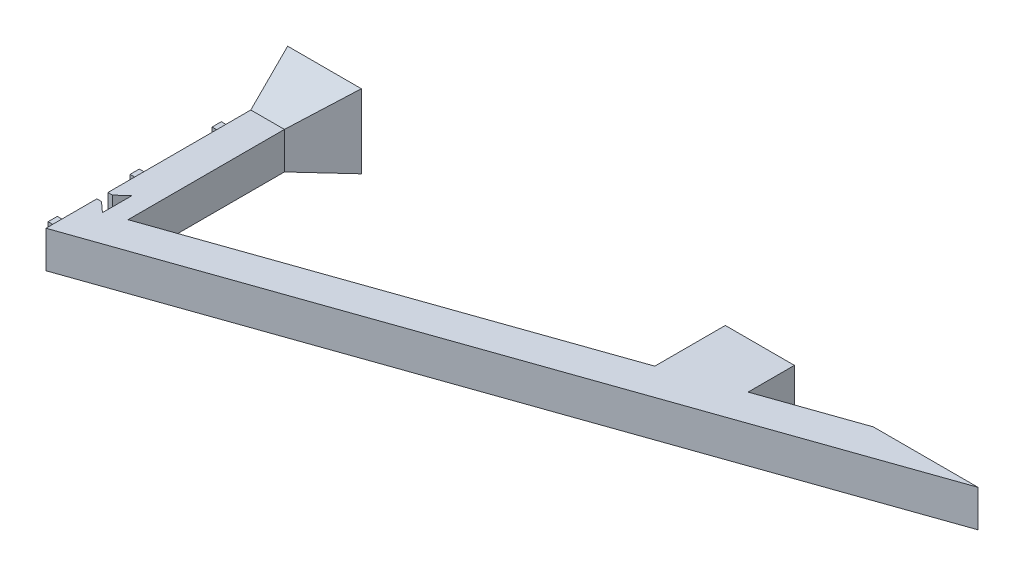
SolidWorks part; units mm, degrees
ref_plane "Přední rovina" through (0, 0, 0) normal (0, 0, 1) x (1, 0, 0)
ref_plane "Horní rovina" through (0, 0, 0) normal (0, 1, 0) x (1, 0, 0)
ref_plane "Pravá rovina" through (0, 0, 0) normal (1, 0, 0) x (0, 0, -1)
sketch "Skica1" plane through (0, 0, 0) normal (0, 1, 0) x (1, 0, 0)
  line L0 (0, 0) -> (0, -55.45)
  line L1 (0, -55.45) -> (149.85, -3)
  line L2 (149.85, -3) -> (127.1478, -3)
  line L3 (127.1478, -3) -> (107, -10.0521)
  line L4 (107, -10.0521) -> (107, 0)
  line L5 (107, 0) -> (92, 0)
  line L6 (92, 0) -> (92, -15.3023)
  line L7 (92, -15.3023) -> (7.3, -44.9487)
  line L8 (7.3, -44.9487) -> (7.3, 0)
  line L9 (7.3, 0) -> (0, 0)
  point P3 (92, -7.6512)
  dimension "D1" = 55.45
  dimension "D2" = 7.3
  dimension "D3" = 15
  dimension "D4" = 3
  dimension "D5" = 7.5
  dimension "D6" = 7.5
  dimension "D7" = 84.7
  dimension "D8" = 149.85
extrude "Přidat vysunutím1" add sketch "Skica1" along normal blind 8
sketch "Skica2" plane through (0, 8, 0) normal (0, 1, 0) x (1, 0, 0)
  line L6 (0, -42) -> (1, -42)
  line L7 (0, 0) -> (0, -55.45) construction
  line L8 (1, -42) -> (3.2, -40)
  line L9 (3.2, -40) -> (3.2, -46.4)
  line L10 (3.2, -46.4) -> (1, -44.4)
  line L11 (1, -44.4) -> (0, -44.4)
  line L12 (0, -44.4) -> (0, -42)
  line L13 (7.3, 0) -> (0, 0) construction
  dimension "D1" = 1
  dimension "D2" = 1
  dimension "D3" = 3.2
  dimension "6,8" = 6.4
  dimension "2,8" = 2.4
  dimension "D4" = 2
  dimension "4" = 40
extrude "Odebrat vysunutím1" cut sketch "Skica2" against normal blind 4.4
sketch "Skica3" plane through (0, 0, 0) normal (-1, 0, 0) x (0, 0, 1)
  line L1 (13.4, 5) -> (15.4, 5)
  line L2 (13.4, 5) -> (13.4, 3)
  line L3 (13.4, 3) -> (15.4, 3)
  line L4 (15.4, 5) -> (15.4, 3)
  line L5 (31.2, 5) -> (33.2, 5)
  line L6 (31.2, 5) -> (31.2, 3)
  line L7 (31.2, 3) -> (33.2, 3)
  line L8 (33.2, 5) -> (33.2, 3)
  line L9 (49, 5) -> (51, 5)
  line L10 (49, 5) -> (49, 3)
  line L11 (49, 3) -> (51, 3)
  line L12 (51, 5) -> (51, 3)
  line L13 (0, 8) -> (0, 0) construction
  line L14 (0, 8) -> (42, 8) construction
  line L15 (44.4, 8) -> (55.45, 8) construction
  dimension "D1" = 2
  dimension "D2" = 2
  dimension "D3" = 2
  dimension "D4" = 2
  dimension "D5" = 2
  dimension "D6" = 2
  dimension "D7" = 13.4
  dimension "D8" = 3
  dimension "D9" = 3
  dimension "D10" = 3
  dimension "D11" = 15.8
  dimension "D12" = 15.8
extrude "Přidat vysunutím2" add sketch "Skica3" along normal blind 4
sketch "Skica5" plane through (0, 8, 0) normal (0, 1, 0) x (1, 0, 0)
  line L0 (0, 0) -> (0, -42) construction
  line L5 (0, -3) -> (16, -3)
  line L6 (0, -3) -> (0, -11)
  line L7 (0, -11) -> (16, -11)
  line L8 (16, -3) -> (16, -11)
  line L9 (7.3, 0) -> (0, 0) construction
  dimension "D1" = 8
  dimension "D2" = 3
  dimension "D3" = 16
extrude "Přidat vysunutím4" add sketch "Skica5" against normal blind 16 from offset 8
sketch "Skica6" plane through (0, 0, 0) normal (-1, 0, 0) x (0, 0, 1)
  line L3 (3, 16) -> (11, 16)
  line L4 (11, 16) -> (11, 8)
  line L5 (11, 8) -> (3, 16)
extrude "Odebrat vysunutím2" cut sketch "Skica6" against normal through all
sketch "Skica7" plane through (0, 0, 0) normal (0, -1, 0) x (1, 0, 0)
  line L3 (7.3, 11) -> (16, 11)
  line L4 (16, 11) -> (16, 3)
  line L5 (16, 3) -> (7.3, 11)
extrude "Odebrat vysunutím3" cut sketch "Skica7" against normal through all
